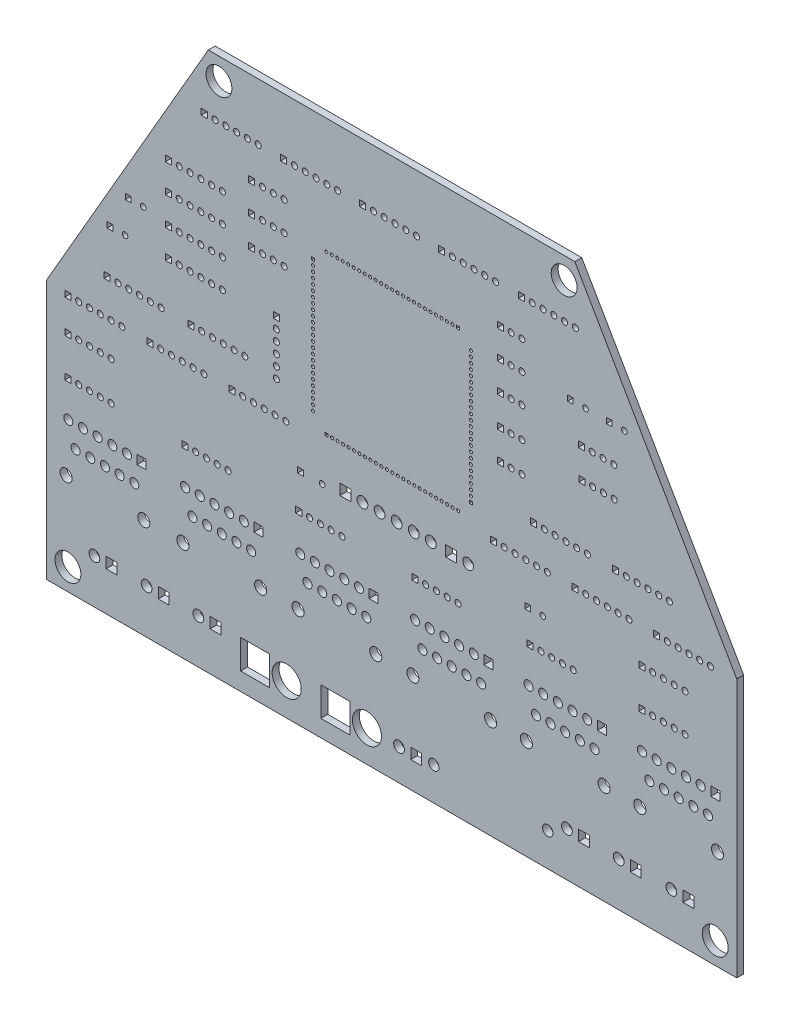
SolidWorks part; units mm, degrees
ref_plane "Plan de face" through (0, 0, 0) normal (0, 0, 1) x (1, 0, 0)
ref_plane "Plan de dessus" through (0, 0, 0) normal (0, 1, 0) x (1, 0, 0)
ref_plane "Plan de droite" through (0, 0, 0) normal (1, 0, 0) x (0, 0, -1)
sketch "Model" plane through (0, 0, 0) normal (0, 0, 1) x (1, 0, 0)
  line L0 (58.25, 50.45) -> (58.25, 51.75)
  line L1 (58.25, 51.75) -> (59.55, 51.75)
  line L2 (59.55, 51.75) -> (59.55, 50.45)
  line L3 (59.55, 50.45) -> (58.25, 50.45)
  line L4 (104.5, 75.5) -> (104.5, 76.9)
  line L5 (104.5, 76.9) -> (105.9, 76.9)
  line L6 (105.9, 76.9) -> (105.9, 75.5)
  line L7 (105.9, 75.5) -> (104.5, 75.5)
  line L8 (104.5, 82.4) -> (104.5, 83.8)
  line L9 (104.5, 83.8) -> (105.9, 83.8)
  line L10 (105.9, 83.8) -> (105.9, 82.4)
  line L11 (105.9, 82.4) -> (104.5, 82.4)
  line L12 (104.5, 89.4) -> (104.5, 90.8)
  line L13 (104.5, 90.8) -> (105.9, 90.8)
  line L14 (105.9, 90.8) -> (105.9, 89.4)
  line L15 (105.9, 89.4) -> (104.5, 89.4)
  line L16 (104.5, 96.1) -> (104.5, 97.5)
  line L17 (104.5, 97.5) -> (105.9, 97.5)
  line L18 (105.9, 97.5) -> (105.9, 96.1)
  line L19 (105.9, 96.1) -> (104.5, 96.1)
  line L20 (104.5, 102.7) -> (104.5, 104.1)
  line L21 (104.5, 104.1) -> (105.9, 104.1)
  line L22 (105.9, 104.1) -> (105.9, 102.7)
  line L23 (105.9, 102.7) -> (104.5, 102.7)
  line L224 (61.45, 95.51) -> (62.15, 95.51)
  line L225 (62.15, 95.51) -> (62.15, 94.81)
  line L226 (62.15, 94.81) -> (61.45, 94.81)
  line L227 (61.45, 94.81) -> (61.45, 95.51)
  line L228 (64.59, 61.15) -> (64.59, 61.85)
  line L229 (64.59, 61.85) -> (65.29, 61.85)
  line L230 (65.29, 61.85) -> (65.29, 61.15)
  line L231 (65.29, 61.15) -> (64.59, 61.15)
  line L232 (95.71, 98.55) -> (95.71, 97.85)
  line L233 (95.71, 97.85) -> (95.01, 97.85)
  line L234 (95.01, 97.85) -> (95.01, 98.55)
  line L235 (95.01, 98.55) -> (95.71, 98.55)
  line L236 (98.75, 64.29) -> (98.05, 64.29)
  line L237 (98.05, 64.29) -> (98.05, 64.99)
  line L238 (98.05, 64.99) -> (98.75, 64.99)
  line L239 (98.75, 64.99) -> (98.75, 64.29)
  line L240 (45.025, 4.125) -> (45.025, 10.875)
  line L241 (45.025, 10.875) -> (51.775, 10.875)
  line L242 (51.775, 10.875) -> (51.775, 4.125)
  line L243 (51.775, 4.125) -> (45.025, 4.125)
  line L244 (63.625, 3.925) -> (63.625, 10.675)
  line L245 (63.625, 10.675) -> (70.375, 10.675)
  line L246 (70.375, 10.675) -> (70.375, 3.925)
  line L247 (70.375, 3.925) -> (63.625, 3.925)
  line L472 (153.98, 35.55) -> (156.08, 35.55)
  line L473 (156.08, 35.55) -> (156.08, 33.45)
  line L474 (156.08, 33.45) -> (153.98, 33.45)
  line L475 (153.98, 33.45) -> (153.98, 35.55)
  line L476 (101.4, 35.63) -> (103.5, 35.63)
  line L477 (103.5, 35.63) -> (103.5, 33.53)
  line L478 (103.5, 33.53) -> (101.4, 33.53)
  line L479 (101.4, 33.53) -> (101.4, 35.63)
  line L480 (74.79, 35.63) -> (76.89, 35.63)
  line L481 (76.89, 35.63) -> (76.89, 33.53)
  line L482 (76.89, 33.53) -> (74.79, 33.53)
  line L483 (74.79, 33.53) -> (74.79, 35.63)
  line L484 (48.11, 35.63) -> (50.21, 35.63)
  line L485 (50.21, 35.63) -> (50.21, 33.53)
  line L486 (50.21, 33.53) -> (48.11, 33.53)
  line L487 (48.11, 33.53) -> (48.11, 35.63)
  line L488 (21.04, 35.63) -> (23.14, 35.63)
  line L489 (23.14, 35.63) -> (23.14, 33.53)
  line L490 (23.14, 33.53) -> (21.04, 33.53)
  line L491 (21.04, 33.53) -> (21.04, 35.63)
  line L492 (127.69, 35.63) -> (129.79, 35.63)
  line L493 (129.79, 35.63) -> (129.79, 33.53)
  line L494 (129.79, 33.53) -> (127.69, 33.53)
  line L495 (127.69, 33.53) -> (127.69, 35.63)
  line L944 (92.55, 50.75) -> (92.55, 53.25)
  line L945 (92.55, 53.25) -> (95.05, 53.25)
  line L946 (95.05, 53.25) -> (95.05, 50.75)
  line L947 (95.05, 50.75) -> (92.55, 50.75)
  line L948 (150.05, 11.45) -> (150.05, 8.95)
  line L949 (150.05, 8.95) -> (147.55, 8.95)
  line L950 (147.55, 8.95) -> (147.55, 11.45)
  line L951 (147.55, 11.45) -> (150.05, 11.45)
  line L952 (137.85, 11.45) -> (137.85, 8.95)
  line L953 (137.85, 8.95) -> (135.35, 8.95)
  line L954 (135.35, 8.95) -> (135.35, 11.45)
  line L955 (135.35, 11.45) -> (137.85, 11.45)
  line L956 (125.85, 11.55) -> (125.85, 9.05)
  line L957 (125.85, 9.05) -> (123.35, 9.05)
  line L958 (123.35, 9.05) -> (123.35, 11.55)
  line L959 (123.35, 11.55) -> (125.85, 11.55)
  line L960 (40.45, 11.55) -> (40.45, 9.05)
  line L961 (40.45, 9.05) -> (37.95, 9.05)
  line L962 (37.95, 9.05) -> (37.95, 11.55)
  line L963 (37.95, 11.55) -> (40.45, 11.55)
  line L964 (28.45, 11.55) -> (28.45, 9.05)
  line L965 (28.45, 9.05) -> (25.95, 9.05)
  line L966 (25.95, 9.05) -> (25.95, 11.55)
  line L967 (25.95, 11.55) -> (28.45, 11.55)
  line L968 (16.35, 11.55) -> (16.35, 9.05)
  line L969 (16.35, 9.05) -> (13.85, 9.05)
  line L970 (13.85, 9.05) -> (13.85, 11.55)
  line L971 (13.85, 11.55) -> (16.35, 11.55)
  line L972 (86.95, 8.55) -> (86.95, 6.05)
  line L973 (86.95, 6.05) -> (84.45, 6.05)
  line L974 (84.45, 6.05) -> (84.45, 8.55)
  line L975 (84.45, 8.55) -> (86.95, 8.55)
  line L992 (68.05, 50.85) -> (68.05, 53.35)
  line L993 (68.05, 53.35) -> (70.55, 53.35)
  line L994 (70.55, 53.35) -> (70.55, 50.85)
  line L995 (70.55, 50.85) -> (68.05, 50.85)
  line L996 (27.6, 77.8) -> (27.6, 79.2)
  line L997 (27.6, 79.2) -> (29, 79.2)
  line L998 (29, 79.2) -> (29, 77.8)
  line L999 (29, 77.8) -> (27.6, 77.8)
  line L1000 (27.6, 84.4) -> (27.6, 85.8)
  line L1001 (27.6, 85.8) -> (29, 85.8)
  line L1002 (29, 85.8) -> (29, 84.4)
  line L1003 (29, 84.4) -> (27.6, 84.4)
  line L1004 (27.6, 91) -> (27.6, 92.4)
  line L1005 (27.6, 92.4) -> (29, 92.4)
  line L1006 (29, 92.4) -> (29, 91)
  line L1007 (29, 91) -> (27.6, 91)
  line L1008 (27.6, 97.6) -> (27.6, 99)
  line L1009 (27.6, 99) -> (29, 99)
  line L1010 (29, 99) -> (29, 97.6)
  line L1011 (29, 97.6) -> (27.6, 97.6)
  line L1012 (23.3, 58.8) -> (23.3, 60.2)
  line L1013 (23.3, 60.2) -> (24.7, 60.2)
  line L1014 (24.7, 60.2) -> (24.7, 58.8)
  line L1015 (24.7, 58.8) -> (23.3, 58.8)
  line L1016 (90.9, 111.1) -> (90.9, 112.5)
  line L1017 (90.9, 112.5) -> (92.3, 112.5)
  line L1018 (92.3, 112.5) -> (92.3, 111.1)
  line L1019 (92.3, 111.1) -> (90.9, 111.1)
  line L1020 (72.6, 111.1) -> (72.6, 112.5)
  line L1021 (72.6, 112.5) -> (74, 112.5)
  line L1022 (74, 112.5) -> (74, 111.1)
  line L1023 (74, 111.1) -> (72.6, 111.1)
  line L1024 (54.3, 111.1) -> (54.3, 112.5)
  line L1025 (54.3, 112.5) -> (55.7, 112.5)
  line L1026 (55.7, 112.5) -> (55.7, 111.1)
  line L1027 (55.7, 111.1) -> (54.3, 111.1)
  line L1028 (35.9, 111.1) -> (35.9, 112.5)
  line L1029 (35.9, 112.5) -> (37.3, 112.5)
  line L1030 (37.3, 112.5) -> (37.3, 111.1)
  line L1031 (37.3, 111.1) -> (35.9, 111.1)
  line L1032 (13.4, 67.1) -> (13.4, 68.5)
  line L1033 (13.4, 68.5) -> (14.8, 68.5)
  line L1034 (14.8, 68.5) -> (14.8, 67.1)
  line L1035 (14.8, 67.1) -> (13.4, 67.1)
  line L1036 (42.3, 58.8) -> (42.3, 60.2)
  line L1037 (42.3, 60.2) -> (43.7, 60.2)
  line L1038 (43.7, 60.2) -> (43.7, 58.8)
  line L1039 (43.7, 58.8) -> (42.3, 58.8)
  line L1040 (4.3, 58.8) -> (4.3, 60.2)
  line L1041 (4.3, 60.2) -> (5.7, 60.2)
  line L1042 (5.7, 60.2) -> (5.7, 58.8)
  line L1043 (5.7, 58.8) -> (4.3, 58.8)
  line L1044 (112.2, 67.1) -> (112.2, 68.5)
  line L1045 (112.2, 68.5) -> (113.6, 68.5)
  line L1046 (113.6, 68.5) -> (113.6, 67.1)
  line L1047 (113.6, 67.1) -> (112.2, 67.1)
  line L1048 (131.2, 67.1) -> (131.2, 68.5)
  line L1049 (131.2, 68.5) -> (132.6, 68.5)
  line L1050 (132.6, 68.5) -> (132.6, 67.1)
  line L1051 (132.6, 67.1) -> (131.2, 67.1)
  line L1052 (102.9, 58.8) -> (102.9, 60.2)
  line L1053 (102.9, 60.2) -> (104.3, 60.2)
  line L1054 (104.3, 60.2) -> (104.3, 58.8)
  line L1055 (104.3, 58.8) -> (102.9, 58.8)
  line L1056 (121.8, 58.8) -> (121.8, 60.2)
  line L1057 (121.8, 60.2) -> (123.2, 60.2)
  line L1058 (123.2, 60.2) -> (123.2, 58.8)
  line L1059 (123.2, 58.8) -> (121.8, 58.8)
  line L1060 (140.7, 58.8) -> (140.7, 60.2)
  line L1061 (140.7, 60.2) -> (142.1, 60.2)
  line L1062 (142.1, 60.2) -> (142.1, 58.8)
  line L1063 (142.1, 58.8) -> (140.7, 58.8)
  line L1064 (32.8, 67.1) -> (32.8, 68.5)
  line L1065 (32.8, 68.5) -> (34.2, 68.5)
  line L1066 (34.2, 68.5) -> (34.2, 67.1)
  line L1067 (34.2, 67.1) -> (32.8, 67.1)
  line L1068 (109.4, 111.1) -> (109.4, 112.5)
  line L1069 (109.4, 112.5) -> (110.8, 112.5)
  line L1070 (110.8, 112.5) -> (110.8, 111.1)
  line L1071 (110.8, 111.1) -> (109.4, 111.1)
  line L1072 (52.6, 80.1) -> (54, 80.1)
  line L1073 (54, 80.1) -> (54, 78.7)
  line L1074 (54, 78.7) -> (52.6, 78.7)
  line L1075 (52.6, 78.7) -> (52.6, 80.1)
  line L1628 (137.3, 50.9) -> (137.3, 52.3)
  line L1629 (137.3, 52.3) -> (138.7, 52.3)
  line L1630 (138.7, 52.3) -> (138.7, 50.9)
  line L1631 (138.7, 50.9) -> (137.3, 50.9)
  line L1632 (4.3, 51.1) -> (4.3, 52.5)
  line L1633 (4.3, 52.5) -> (5.7, 52.5)
  line L1634 (5.7, 52.5) -> (5.7, 51.1)
  line L1635 (5.7, 51.1) -> (4.3, 51.1)
  line L1636 (137.3, 42.2) -> (137.3, 43.6)
  line L1637 (137.3, 43.6) -> (138.7, 43.6)
  line L1638 (138.7, 43.6) -> (138.7, 42.2)
  line L1639 (138.7, 42.2) -> (137.3, 42.2)
  line L1640 (111.4, 42.2) -> (111.4, 43.6)
  line L1641 (111.4, 43.6) -> (112.8, 43.6)
  line L1642 (112.8, 43.6) -> (112.8, 42.2)
  line L1643 (112.8, 42.2) -> (111.4, 42.2)
  line L1644 (84.7, 42.2) -> (84.7, 43.6)
  line L1645 (84.7, 43.6) -> (86.1, 43.6)
  line L1646 (86.1, 43.6) -> (86.1, 42.2)
  line L1647 (86.1, 42.2) -> (84.7, 42.2)
  line L1648 (57.8, 42.2) -> (57.8, 43.6)
  line L1649 (57.8, 43.6) -> (59.2, 43.6)
  line L1650 (59.2, 43.6) -> (59.2, 42.2)
  line L1651 (59.2, 42.2) -> (57.8, 42.2)
  line L1652 (4.3, 42.15) -> (4.3, 43.55)
  line L1653 (4.3, 43.55) -> (5.7, 43.55)
  line L1654 (5.7, 43.55) -> (5.7, 42.15)
  line L1655 (5.7, 42.15) -> (4.3, 42.15)
  line L1656 (31.4, 42.2) -> (31.4, 43.6)
  line L1657 (31.4, 43.6) -> (32.8, 43.6)
  line L1658 (32.8, 43.6) -> (32.8, 42.2)
  line L1659 (32.8, 42.2) -> (31.4, 42.2)
  line L1660 (123.4, 81.2) -> (123.4, 82.6)
  line L1661 (123.4, 82.6) -> (124.8, 82.6)
  line L1662 (124.8, 82.6) -> (124.8, 81.2)
  line L1663 (124.8, 81.2) -> (123.4, 81.2)
  line L1664 (123.3, 88.1) -> (123.3, 89.5)
  line L1665 (123.3, 89.5) -> (124.7, 89.5)
  line L1666 (124.7, 89.5) -> (124.7, 88.1)
  line L1667 (124.7, 88.1) -> (123.3, 88.1)
  line L1668 (46.9, 89.7) -> (46.9, 91.1)
  line L1669 (46.9, 91.1) -> (48.3, 91.1)
  line L1670 (48.3, 91.1) -> (48.3, 89.7)
  line L1671 (48.3, 89.7) -> (46.9, 89.7)
  line L1672 (46.9, 96.4) -> (46.9, 97.8)
  line L1673 (46.9, 97.8) -> (48.3, 97.8)
  line L1674 (48.3, 97.8) -> (48.3, 96.4)
  line L1675 (48.3, 96.4) -> (46.9, 96.4)
  line L1676 (46.9, 103.1) -> (46.9, 104.5)
  line L1677 (46.9, 104.5) -> (48.3, 104.5)
  line L1678 (48.3, 104.5) -> (48.3, 103.1)
  line L1679 (48.3, 103.1) -> (46.9, 103.1)
  line L1680 (110.9, 49.55) -> (110.9, 50.85)
  line L1681 (110.9, 50.85) -> (112.2, 50.85)
  line L1682 (112.2, 50.85) -> (112.2, 49.55)
  line L1683 (112.2, 49.55) -> (110.9, 49.55)
  line L1684 (120.8, 96.15) -> (120.8, 97.45)
  line L1685 (120.8, 97.45) -> (122.1, 97.45)
  line L1686 (122.1, 97.45) -> (122.1, 96.15)
  line L1687 (122.1, 96.15) -> (120.8, 96.15)
  line L1688 (129.8, 96.15) -> (129.8, 97.45)
  line L1689 (129.8, 97.45) -> (131.1, 97.45)
  line L1690 (131.1, 97.45) -> (131.1, 96.15)
  line L1691 (131.1, 96.15) -> (129.8, 96.15)
  line L1692 (18.3, 85.35) -> (18.3, 86.65)
  line L1693 (18.3, 86.65) -> (19.6, 86.65)
  line L1694 (19.6, 86.65) -> (19.6, 85.35)
  line L1695 (19.6, 85.35) -> (18.3, 85.35)
  line L1696 (14.1, 77.55) -> (14.1, 78.85)
  line L1697 (14.1, 78.85) -> (15.4, 78.85)
  line L1698 (15.4, 78.85) -> (15.4, 77.55)
  line L1699 (15.4, 77.55) -> (14.1, 77.55)
  line L1700 (0, 0) -> (160, 0)
  line L1701 (160, 0) -> (160, 60)
  line L1702 (160, 60) -> (122.47, 125)
  line L1703 (122.47, 125) -> (37.53, 125)
  line L1704 (37.53, 125) -> (0, 60)
  line L1705 (0, 60) -> (0, 0)
  circle A0 centre (63.9, 51.1) radius 0.65
  circle A1 centre (107.7, 76.2) radius 0.7
  circle A2 centre (110.2, 76.2) radius 0.7
  circle A3 centre (107.7, 83.1) radius 0.7
  circle A4 centre (110.2, 83.1) radius 0.7
  circle A5 centre (107.7, 90.1) radius 0.7
  circle A6 centre (110.2, 90.1) radius 0.7
  circle A7 centre (107.7, 96.8) radius 0.7
  circle A8 centre (110.2, 96.8) radius 0.7
  circle A9 centre (107.7, 103.4) radius 0.7
  circle A10 centre (110.2, 103.4) radius 0.7
  circle A11 centre (89.8, 7.7) radius 1.2
  circle A12 centre (116.2, 7.7) radius 1.2
  circle A13 centre (61.8, 93.89) radius 0.35
  circle A14 centre (61.8, 92.62) radius 0.35
  circle A15 centre (61.8, 91.35) radius 0.35
  circle A16 centre (61.8, 90.08) radius 0.35
  circle A17 centre (61.8, 88.81) radius 0.35
  circle A18 centre (61.8, 87.54) radius 0.35
  circle A19 centre (61.8, 86.27) radius 0.35
  circle A20 centre (61.8, 85) radius 0.35
  circle A21 centre (61.8, 83.73) radius 0.35
  circle A22 centre (61.8, 82.46) radius 0.35
  circle A23 centre (61.8, 81.19) radius 0.35
  circle A24 centre (61.8, 79.92) radius 0.35
  circle A25 centre (61.8, 78.65) radius 0.35
  circle A26 centre (61.8, 77.38) radius 0.35
  circle A27 centre (61.8, 76.11) radius 0.35
  circle A28 centre (61.8, 74.84) radius 0.35
  circle A29 centre (61.8, 73.57) radius 0.35
  circle A30 centre (61.8, 72.3) radius 0.35
  circle A31 centre (61.8, 71.03) radius 0.35
  circle A32 centre (61.8, 69.76) radius 0.35
  circle A33 centre (61.8, 68.49) radius 0.35
  circle A34 centre (61.8, 67.22) radius 0.35
  circle A35 centre (61.8, 65.95) radius 0.35
  circle A36 centre (61.8, 64.68) radius 0.35
  circle A37 centre (66.21, 61.5) radius 0.35
  circle A38 centre (67.48, 61.5) radius 0.35
  circle A39 centre (68.75, 61.5) radius 0.35
  circle A40 centre (70.02, 61.5) radius 0.35
  circle A41 centre (71.29, 61.5) radius 0.35
  circle A42 centre (72.56, 61.5) radius 0.35
  circle A43 centre (73.83, 61.5) radius 0.35
  circle A44 centre (75.1, 61.5) radius 0.35
  circle A45 centre (76.37, 61.5) radius 0.35
  circle A46 centre (77.64, 61.5) radius 0.35
  circle A47 centre (78.91, 61.5) radius 0.35
  circle A48 centre (80.18, 61.5) radius 0.35
  circle A49 centre (81.45, 61.5) radius 0.35
  circle A50 centre (82.72, 61.5) radius 0.35
  circle A51 centre (83.99, 61.5) radius 0.35
  circle A52 centre (85.26, 61.5) radius 0.35
  circle A53 centre (86.53, 61.5) radius 0.35
  circle A54 centre (87.8, 61.5) radius 0.35
  circle A55 centre (89.07, 61.5) radius 0.35
  circle A56 centre (90.34, 61.5) radius 0.35
  circle A57 centre (91.61, 61.5) radius 0.35
  circle A58 centre (92.88, 61.5) radius 0.35
  circle A59 centre (94.15, 61.5) radius 0.35
  circle A60 centre (95.42, 61.5) radius 0.35
  circle A61 centre (94.09, 98.2) radius 0.35
  circle A62 centre (92.82, 98.2) radius 0.35
  circle A63 centre (91.55, 98.2) radius 0.35
  circle A64 centre (90.28, 98.2) radius 0.35
  circle A65 centre (89.01, 98.2) radius 0.35
  circle A66 centre (87.74, 98.2) radius 0.35
  circle A67 centre (86.47, 98.2) radius 0.35
  circle A68 centre (85.2, 98.2) radius 0.35
  circle A69 centre (83.93, 98.2) radius 0.35
  circle A70 centre (82.66, 98.2) radius 0.35
  circle A71 centre (81.39, 98.2) radius 0.35
  circle A72 centre (80.12, 98.2) radius 0.35
  circle A73 centre (78.85, 98.2) radius 0.35
  circle A74 centre (77.58, 98.2) radius 0.35
  circle A75 centre (76.31, 98.2) radius 0.35
  circle A76 centre (75.04, 98.2) radius 0.35
  circle A77 centre (73.77, 98.2) radius 0.35
  circle A78 centre (72.5, 98.2) radius 0.35
  circle A79 centre (71.23, 98.2) radius 0.35
  circle A80 centre (69.96, 98.2) radius 0.35
  circle A81 centre (68.69, 98.2) radius 0.35
  circle A82 centre (67.42, 98.2) radius 0.35
  circle A83 centre (66.15, 98.2) radius 0.35
  circle A84 centre (64.88, 98.2) radius 0.35
  circle A85 centre (98.4, 65.91) radius 0.35
  circle A86 centre (98.4, 67.18) radius 0.35
  circle A87 centre (98.4, 68.45) radius 0.35
  circle A88 centre (98.4, 69.72) radius 0.35
  circle A89 centre (98.4, 70.99) radius 0.35
  circle A90 centre (98.4, 72.26) radius 0.35
  circle A91 centre (98.4, 73.53) radius 0.35
  circle A92 centre (98.4, 74.8) radius 0.35
  circle A93 centre (98.4, 76.07) radius 0.35
  circle A94 centre (98.4, 77.34) radius 0.35
  circle A95 centre (98.4, 78.61) radius 0.35
  circle A96 centre (98.4, 79.88) radius 0.35
  circle A97 centre (98.4, 81.15) radius 0.35
  circle A98 centre (98.4, 82.42) radius 0.35
  circle A99 centre (98.4, 83.69) radius 0.35
  circle A100 centre (98.4, 84.96) radius 0.35
  circle A101 centre (98.4, 86.23) radius 0.35
  circle A102 centre (98.4, 87.5) radius 0.35
  circle A103 centre (98.4, 88.77) radius 0.35
  circle A104 centre (98.4, 90.04) radius 0.35
  circle A105 centre (98.4, 91.31) radius 0.35
  circle A106 centre (98.4, 92.58) radius 0.35
  circle A107 centre (98.4, 93.85) radius 0.35
  circle A108 centre (98.4, 95.12) radius 0.35
  circle A109 centre (55.7, 7.5) radius 3.375
  circle A110 centre (74.3, 7.3) radius 3.375
  circle A111 centre (153.33, 29.42) radius 1.05
  circle A112 centre (151.63, 34.5) radius 1.05
  circle A113 centre (149.93, 29.42) radius 1.05
  circle A114 centre (148.23, 34.5) radius 1.05
  circle A115 centre (146.53, 29.42) radius 1.05
  circle A116 centre (144.83, 34.5) radius 1.05
  circle A117 centre (143.13, 29.42) radius 1.05
  circle A118 centre (141.43, 34.5) radius 1.05
  circle A119 centre (139.73, 29.42) radius 1.05
  circle A120 centre (138.03, 34.5) radius 1.05
  circle A121 centre (155.53, 23.1) radius 1.4
  circle A122 centre (137.53, 23.1) radius 1.4
  circle A123 centre (100.75, 29.5) radius 1.05
  circle A124 centre (99.05, 34.58) radius 1.05
  circle A125 centre (97.35, 29.5) radius 1.05
  circle A126 centre (95.65, 34.58) radius 1.05
  circle A127 centre (93.95, 29.5) radius 1.05
  circle A128 centre (92.25, 34.58) radius 1.05
  circle A129 centre (90.55, 29.5) radius 1.05
  circle A130 centre (88.85, 34.58) radius 1.05
  circle A131 centre (87.15, 29.5) radius 1.05
  circle A132 centre (85.45, 34.58) radius 1.05
  circle A133 centre (102.95, 23.18) radius 1.4
  circle A134 centre (84.95, 23.18) radius 1.4
  circle A135 centre (74.14, 29.5) radius 1.05
  circle A136 centre (72.44, 34.58) radius 1.05
  circle A137 centre (70.74, 29.5) radius 1.05
  circle A138 centre (69.04, 34.58) radius 1.05
  circle A139 centre (67.34, 29.5) radius 1.05
  circle A140 centre (65.64, 34.58) radius 1.05
  circle A141 centre (63.94, 29.5) radius 1.05
  circle A142 centre (62.24, 34.58) radius 1.05
  circle A143 centre (60.54, 29.5) radius 1.05
  circle A144 centre (58.84, 34.58) radius 1.05
  circle A145 centre (76.34, 23.18) radius 1.4
  circle A146 centre (58.34, 23.18) radius 1.4
  circle A147 centre (47.46, 29.5) radius 1.05
  circle A148 centre (45.76, 34.58) radius 1.05
  circle A149 centre (44.06, 29.5) radius 1.05
  circle A150 centre (42.36, 34.58) radius 1.05
  circle A151 centre (40.66, 29.5) radius 1.05
  circle A152 centre (38.96, 34.58) radius 1.05
  circle A153 centre (37.26, 29.5) radius 1.05
  circle A154 centre (35.56, 34.58) radius 1.05
  circle A155 centre (33.86, 29.5) radius 1.05
  circle A156 centre (32.16, 34.58) radius 1.05
  circle A157 centre (49.66, 23.18) radius 1.4
  circle A158 centre (31.66, 23.18) radius 1.4
  circle A159 centre (20.39, 29.5) radius 1.05
  circle A160 centre (18.69, 34.58) radius 1.05
  circle A161 centre (16.99, 29.5) radius 1.05
  circle A162 centre (15.29, 34.58) radius 1.05
  circle A163 centre (13.59, 29.5) radius 1.05
  circle A164 centre (11.89, 34.58) radius 1.05
  circle A165 centre (10.19, 29.5) radius 1.05
  circle A166 centre (8.49, 34.58) radius 1.05
  circle A167 centre (6.79, 29.5) radius 1.05
  circle A168 centre (5.09, 34.58) radius 1.05
  circle A169 centre (22.59, 23.18) radius 1.4
  circle A170 centre (4.59, 23.18) radius 1.4
  circle A171 centre (127.04, 29.5) radius 1.05
  circle A172 centre (125.34, 34.58) radius 1.05
  circle A173 centre (123.64, 29.5) radius 1.05
  circle A174 centre (121.94, 34.58) radius 1.05
  circle A175 centre (120.24, 29.5) radius 1.05
  circle A176 centre (118.54, 34.58) radius 1.05
  circle A177 centre (116.84, 29.5) radius 1.05
  circle A178 centre (115.14, 34.58) radius 1.05
  circle A179 centre (113.44, 29.5) radius 1.05
  circle A180 centre (111.74, 34.58) radius 1.05
  circle A181 centre (129.24, 23.18) radius 1.4
  circle A182 centre (111.24, 23.18) radius 1.4
  circle A183 centre (97.76, 52) radius 1.25
  circle A184 centre (144.84, 10.2) radius 1.25
  circle A185 centre (132.64, 10.2) radius 1.25
  circle A186 centre (120.64, 10.3) radius 1.25
  circle A187 centre (35.24, 10.3) radius 1.25
  circle A188 centre (23.24, 10.3) radius 1.25
  circle A189 centre (11.14, 10.3) radius 1.25
  circle A190 centre (81.74, 7.3) radius 1.25
  circle A191 centre (120, 120) radius 3
  circle A192 centre (40, 120) radius 3
  circle A193 centre (5, 5) radius 3
  circle A194 centre (155, 5) radius 3
  circle A195 centre (73.26, 52.1) radius 1.25
  circle A196 centre (77.22, 52.1) radius 1.25
  circle A197 centre (81.18, 52.1) radius 1.25
  circle A198 centre (85.14, 52.1) radius 1.25
  circle A199 centre (89.1, 52.1) radius 1.25
  circle A200 centre (30.8, 78.5) radius 0.7
  circle A201 centre (33.3, 78.5) radius 0.7
  circle A202 centre (35.8, 78.5) radius 0.7
  circle A203 centre (38.3, 78.5) radius 0.7
  circle A204 centre (40.8, 78.5) radius 0.7
  circle A205 centre (30.8, 85.1) radius 0.7
  circle A206 centre (33.3, 85.1) radius 0.7
  circle A207 centre (35.8, 85.1) radius 0.7
  circle A208 centre (38.3, 85.1) radius 0.7
  circle A209 centre (40.8, 85.1) radius 0.7
  circle A210 centre (30.8, 91.7) radius 0.7
  circle A211 centre (33.3, 91.7) radius 0.7
  circle A212 centre (35.8, 91.7) radius 0.7
  circle A213 centre (38.3, 91.7) radius 0.7
  circle A214 centre (40.8, 91.7) radius 0.7
  circle A215 centre (30.8, 98.3) radius 0.7
  circle A216 centre (33.3, 98.3) radius 0.7
  circle A217 centre (35.8, 98.3) radius 0.7
  circle A218 centre (38.3, 98.3) radius 0.7
  circle A219 centre (40.8, 98.3) radius 0.7
  circle A220 centre (26.5, 59.5) radius 0.7
  circle A221 centre (29, 59.5) radius 0.7
  circle A222 centre (31.5, 59.5) radius 0.7
  circle A223 centre (34, 59.5) radius 0.7
  circle A224 centre (36.5, 59.5) radius 0.7
  circle A225 centre (94.1, 111.8) radius 0.7
  circle A226 centre (96.6, 111.8) radius 0.7
  circle A227 centre (99.1, 111.8) radius 0.7
  circle A228 centre (101.6, 111.8) radius 0.7
  circle A229 centre (104.1, 111.8) radius 0.7
  circle A230 centre (75.8, 111.8) radius 0.7
  circle A231 centre (78.3, 111.8) radius 0.7
  circle A232 centre (80.8, 111.8) radius 0.7
  circle A233 centre (83.3, 111.8) radius 0.7
  circle A234 centre (85.8, 111.8) radius 0.7
  circle A235 centre (57.5, 111.8) radius 0.7
  circle A236 centre (60, 111.8) radius 0.7
  circle A237 centre (62.5, 111.8) radius 0.7
  circle A238 centre (65, 111.8) radius 0.7
  circle A239 centre (67.5, 111.8) radius 0.7
  circle A240 centre (39.1, 111.8) radius 0.7
  circle A241 centre (41.6, 111.8) radius 0.7
  circle A242 centre (44.1, 111.8) radius 0.7
  circle A243 centre (46.6, 111.8) radius 0.7
  circle A244 centre (49.1, 111.8) radius 0.7
  circle A245 centre (16.6, 67.8) radius 0.7
  circle A246 centre (19.1, 67.8) radius 0.7
  circle A247 centre (21.6, 67.8) radius 0.7
  circle A248 centre (24.1, 67.8) radius 0.7
  circle A249 centre (26.6, 67.8) radius 0.7
  circle A250 centre (45.5, 59.5) radius 0.7
  circle A251 centre (48, 59.5) radius 0.7
  circle A252 centre (50.5, 59.5) radius 0.7
  circle A253 centre (53, 59.5) radius 0.7
  circle A254 centre (55.5, 59.5) radius 0.7
  circle A255 centre (7.5, 59.5) radius 0.7
  circle A256 centre (10, 59.5) radius 0.7
  circle A257 centre (12.5, 59.5) radius 0.7
  circle A258 centre (15, 59.5) radius 0.7
  circle A259 centre (17.5, 59.5) radius 0.7
  circle A260 centre (115.4, 67.8) radius 0.7
  circle A261 centre (117.9, 67.8) radius 0.7
  circle A262 centre (120.4, 67.8) radius 0.7
  circle A263 centre (122.9, 67.8) radius 0.7
  circle A264 centre (125.4, 67.8) radius 0.7
  circle A265 centre (134.4, 67.8) radius 0.7
  circle A266 centre (136.9, 67.8) radius 0.7
  circle A267 centre (139.4, 67.8) radius 0.7
  circle A268 centre (141.9, 67.8) radius 0.7
  circle A269 centre (144.4, 67.8) radius 0.7
  circle A270 centre (106.1, 59.5) radius 0.7
  circle A271 centre (108.6, 59.5) radius 0.7
  circle A272 centre (111.1, 59.5) radius 0.7
  circle A273 centre (113.6, 59.5) radius 0.7
  circle A274 centre (116.1, 59.5) radius 0.7
  circle A275 centre (125, 59.5) radius 0.7
  circle A276 centre (127.5, 59.5) radius 0.7
  circle A277 centre (130, 59.5) radius 0.7
  circle A278 centre (132.5, 59.5) radius 0.7
  circle A279 centre (135, 59.5) radius 0.7
  circle A280 centre (143.9, 59.5) radius 0.7
  circle A281 centre (146.4, 59.5) radius 0.7
  circle A282 centre (148.9, 59.5) radius 0.7
  circle A283 centre (151.4, 59.5) radius 0.7
  circle A284 centre (153.9, 59.5) radius 0.7
  circle A285 centre (36, 67.8) radius 0.7
  circle A286 centre (38.5, 67.8) radius 0.7
  circle A287 centre (41, 67.8) radius 0.7
  circle A288 centre (43.5, 67.8) radius 0.7
  circle A289 centre (46, 67.8) radius 0.7
  circle A290 centre (112.6, 111.8) radius 0.7
  circle A291 centre (115.1, 111.8) radius 0.7
  circle A292 centre (117.6, 111.8) radius 0.7
  circle A293 centre (120.1, 111.8) radius 0.7
  circle A294 centre (122.6, 111.8) radius 0.7
  circle A295 centre (53.3, 76.9) radius 0.7
  circle A296 centre (53.3, 74.4) radius 0.7
  circle A297 centre (53.3, 71.9) radius 0.7
  circle A298 centre (53.3, 69.4) radius 0.7
  circle A299 centre (53.3, 66.9) radius 0.7
  circle A300 centre (140.5, 51.6) radius 0.7
  circle A301 centre (143, 51.6) radius 0.7
  circle A302 centre (145.5, 51.6) radius 0.7
  circle A303 centre (148, 51.6) radius 0.7
  circle A304 centre (7.5, 51.8) radius 0.7
  circle A305 centre (10, 51.8) radius 0.7
  circle A306 centre (12.5, 51.8) radius 0.7
  circle A307 centre (15, 51.8) radius 0.7
  circle A308 centre (140.5, 42.9) radius 0.7
  circle A309 centre (143, 42.9) radius 0.7
  circle A310 centre (145.5, 42.9) radius 0.7
  circle A311 centre (148, 42.9) radius 0.7
  circle A312 centre (114.6, 42.9) radius 0.7
  circle A313 centre (117.1, 42.9) radius 0.7
  circle A314 centre (119.6, 42.9) radius 0.7
  circle A315 centre (122.1, 42.9) radius 0.7
  circle A316 centre (87.9, 42.9) radius 0.7
  circle A317 centre (90.4, 42.9) radius 0.7
  circle A318 centre (92.9, 42.9) radius 0.7
  circle A319 centre (95.4, 42.9) radius 0.7
  circle A320 centre (61, 42.9) radius 0.7
  circle A321 centre (63.5, 42.9) radius 0.7
  circle A322 centre (66, 42.9) radius 0.7
  circle A323 centre (68.5, 42.9) radius 0.7
  circle A324 centre (7.5, 42.85) radius 0.7
  circle A325 centre (10, 42.85) radius 0.7
  circle A326 centre (12.5, 42.85) radius 0.7
  circle A327 centre (15, 42.85) radius 0.7
  circle A328 centre (34.6, 42.9) radius 0.7
  circle A329 centre (37.1, 42.9) radius 0.7
  circle A330 centre (39.6, 42.9) radius 0.7
  circle A331 centre (42.1, 42.9) radius 0.7
  circle A332 centre (126.6, 81.9) radius 0.7
  circle A333 centre (129.1, 81.9) radius 0.7
  circle A334 centre (131.6, 81.9) radius 0.7
  circle A335 centre (126.5, 88.8) radius 0.7
  circle A336 centre (129, 88.8) radius 0.7
  circle A337 centre (131.5, 88.8) radius 0.7
  circle A338 centre (50.1, 90.4) radius 0.7
  circle A339 centre (52.6, 90.4) radius 0.7
  circle A340 centre (55.1, 90.4) radius 0.7
  circle A341 centre (50.1, 97.1) radius 0.7
  circle A342 centre (52.6, 97.1) radius 0.7
  circle A343 centre (55.1, 97.1) radius 0.7
  circle A344 centre (50.1, 103.8) radius 0.7
  circle A345 centre (52.6, 103.8) radius 0.7
  circle A346 centre (55.1, 103.8) radius 0.7
  circle A347 centre (115.05, 50.2) radius 0.65
  circle A348 centre (124.95, 96.8) radius 0.65
  circle A349 centre (133.95, 96.8) radius 0.65
  circle A350 centre (22.45, 86) radius 0.65
  circle A351 centre (18.25, 78.2) radius 0.65
extrude "Boss.-Extru.1" add sketch "Model" along normal blind 1.6
